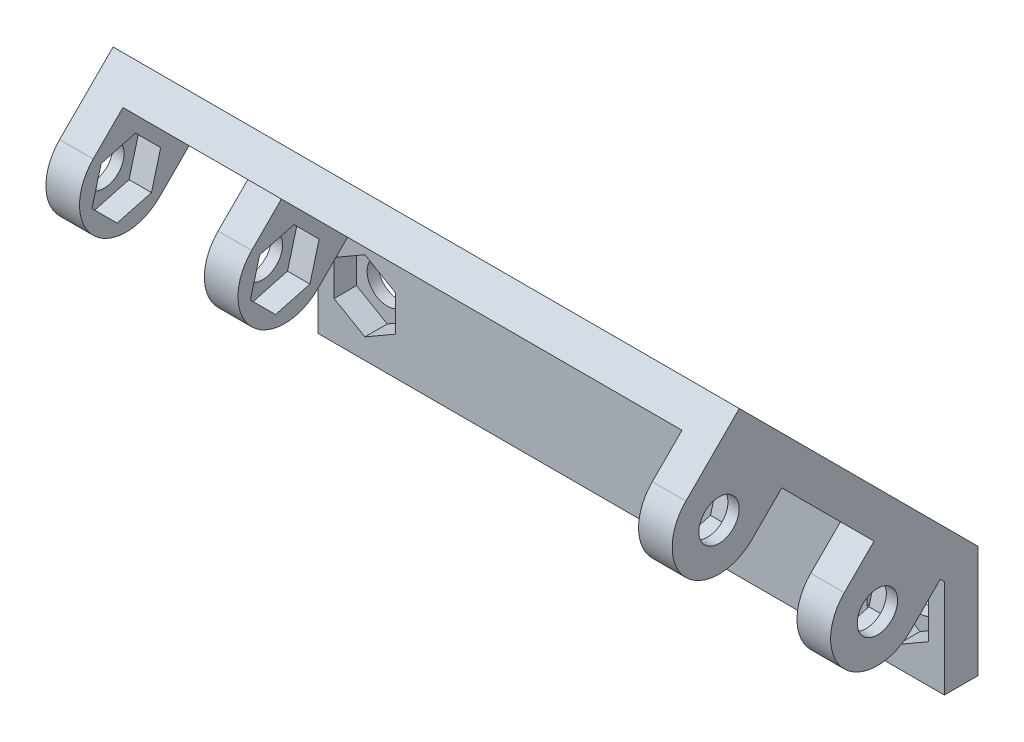
SolidWorks part; units mm, degrees
ref_plane "Front Plane" through (0, 0, 0) normal (0, 0, 1) x (1, 0, 0)
ref_plane "Top Plane" through (0, 0, 0) normal (0, 1, 0) x (1, 0, 0)
ref_plane "Right Plane" through (0, 0, 0) normal (1, 0, 0) x (0, 0, -1)
sketch "Sketch1" plane through (0, 0, 0) normal (0, 0, 1) x (1, 0, 0)
  line L1 (70.0719, -10) -> (14.1792, -10)
  line L2 (70.0719, -10) -> (70.0719, 0)
  line L3 (70.0719, 0) -> (14.1792, 0)
  line L4 (14.1792, -10) -> (14.1792, 0)
extrude "Boss-Extrude1" add sketch "Sketch1" along normal blind 3
sketch "Sketch2" plane through (0, 0, 3) normal (0, 0, 1) x (1, 0, 0)
  line L2 (22.5208, -10) -> (22.5208, 0) construction
  line L3 (14.1792, 0) -> (14.1792, -10) construction
  line L6 (22.5208, -10) -> (22.5208, 0) construction
  line L7 (14.1792, 0) -> (14.1792, -10) construction
  line L8 (42.1255, 0) -> (42.1255, -10) construction
  line L15 (70.0719, 0) -> (14.1792, 0) construction
  line L25 (14.1792, -10) -> (70.0719, -10) construction
  line L26 (14.1792, -5) -> (22.5208, -5) construction
  line L27 (65.9011, -8.1754) -> (63.1511, -6.5877)
  line L28 (21.1, -6.5877) -> (21.1, -3.4123)
  line L29 (21.1, -3.4123) -> (18.35, -1.8246)
  line L30 (18.35, -1.8246) -> (15.6, -3.4123)
  line L31 (15.6, -3.4123) -> (15.6, -6.5877)
  line L32 (15.6, -6.5877) -> (18.35, -8.1754)
  line L33 (18.35, -8.1754) -> (21.1, -6.5877)
  line L34 (68.6511, -6.5877) -> (65.9011, -8.1754)
  line L35 (68.6511, -3.4123) -> (68.6511, -6.5877)
  line L36 (65.9011, -1.8246) -> (68.6511, -3.4123)
  line L37 (63.1511, -3.4123) -> (65.9011, -1.8246)
  line L38 (63.1511, -6.5877) -> (63.1511, -3.4123)
  circle A0 centre (18.35, -5) radius 2.75 construction
  circle A1 centre (65.9011, -5) radius 2.75 construction
  point P14 (15.6, -5)
  dimension "D1" = 5.5
extrude "Cut-Extrude1" cut sketch "Sketch2" against normal blind 2
sketch "Sketch3" plane through (0, 0, 3) normal (0, 0, 1) x (1, 0, 0)
  point P8 (18.35, -5)
  point P11 (65.9011, -5)
hole_wizard "M3 Clearance Hole1" positions "Sketch3" profile "Sketch4" hole size "M3" standard "ANSI Metric" end condition through all
sketch "Sketch4" plane through (18.35, -5, 3) normal (1, 0, 0) x (0, -1, 0)
  line L0 (0, 0) -> (0, 3)
  line L1 (0, 3) -> (1.8, 3)
  line L2 (1.8, 3) -> (1.8, 0)
  line L5 (1.8, 0) -> (0, 0)
  line L11 (0, -6.35) -> (0, 107.95) construction
  dimension "Thru Hole Dia." = 3.6
  dimension "Thru Hole Depth" = 3
sketch "Sketch5" plane through (14.1792, 0, 0) normal (-1, 0, 0) x (0, 0, 1)
  line L0 (0, 0) -> (21.299, 21.299)
  line L1 (21.299, 21.299) -> (23.4203, 19.1777)
  line L2 (23.4203, 19.1777) -> (3, -1.2426)
  line L3 (3, 0) -> (3, -10) construction
  line L4 (3, 0) -> (0, 0) construction
  line L5 (3, 0) -> (22.799, 19.799) construction
  line L6 (3, -1.2426) -> (3, 0)
  line L7 (3, 0) -> (0, 0)
  dimension "D1" = 45
  dimension "D2" = 3
  dimension "D3" = 28
extrude "Boss-Extrude2" add sketch "Sketch5" against normal up to surface (55.8926 mm away) up to face at (70.0719, -5, 1.5)
sketch "Sketch6" plane through (14.1792, 0, 0) normal (-1, 0, 0) x (0, 0, 1)
  line L0 (23.4203, 19.1777) -> (17.5154, 13.2727)
  line L1 (3, -1.2426) -> (23.4203, 19.1777) construction
  line L2 (23.4203, 19.1777) -> (26.072, 16.526)
  line L3 (17.5154, 13.2727) -> (20.167, 10.6211)
  line L4 (11.2754, 11.2754) -> (13.3968, 9.1541) construction
  line L5 (20.8741, 11.3282) -> (23.9413, 10.5063)
  line L6 (23.9413, 10.5063) -> (26.1867, 12.7517)
  line L7 (26.1867, 12.7517) -> (25.3649, 15.8189)
  line L8 (25.3649, 15.8189) -> (22.2976, 16.6408)
  line L9 (22.2976, 16.6408) -> (20.0523, 14.3954)
  line L10 (20.0523, 14.3954) -> (20.8741, 11.3282)
  line L12 (21.299, 21.299) -> (0, 0) construction
  line L13 (5.9101, 0.2533) -> (8.1555, 2.4986)
  line L14 (6.732, -2.814) -> (5.9101, 0.2533)
  line L15 (9.7992, -3.6358) -> (6.732, -2.814)
  line L16 (12.0446, -1.3904) -> (9.7992, -3.6358)
  line L17 (11.2227, 1.6768) -> (12.0446, -1.3904)
  line L18 (8.1555, 2.4986) -> (11.2227, 1.6768)
  line L19 (3.3732, -0.8694) -> (6.0249, -3.5211)
  line L20 (3.3732, -0.8694) -> (9.2782, 5.0355)
  line L21 (9.2782, 5.0355) -> (11.9298, 2.3839)
  arc A0 (26.072, 16.526) -> (20.167, 10.6211) centre (23.1195, 13.5735) cw
  circle A2 centre (23.1195, 13.5735) radius 2.75 construction
  circle A3 centre (8.9774, -0.5686) radius 2.75 construction
  arc A4 (6.0249, -3.5211) -> (11.9298, 2.3839) centre (8.9774, -0.5686) ccw
  point P8 (0, 0)
  point P9 (0, 0)
  point P19 (9.8603, 9.8603)
  point P22 (11.548, 7.3053)
  line M10 (3, -1.2426) -> (23.4203, 19.1777)
  dimension "D3" = 3.75
  dimension "D1" = 1
  dimension "D4" = 5.5
  dimension "D5" = 10
extrude "Boss-Extrude3" add sketch "Sketch6" against normal blind 3 contours L19 A4 L21 L13 L18 L17 L16 L15 L14 M10 | L18 L13 L14 L15 L16 L17 | L9 L10 L5 L6 L7 L8 | A0 L2 L3 L10 L9 L8 L7 L6 L5 M10 region at (14.1792, 17.754, 24.6483) region at (14.1792, 3.6119, 10.5062) region at (14.1792, 13.5735, 23.1195) region at (14.1792, -0.5686, 8.9774)
ref_plane "Plane1" through (42.1255, 0, 0) normal (-1, 0, 0) x (0, 0, 1)
mirror "Mirror1" about plane through (42.1255, 0, 0) normal (-1, 0, 0) of "Boss-Extrude3"
sketch "Sketch7" plane through (14.1792, 0, 0) normal (-1, 0, 0) x (0, 0, 1)
  point P0 (8.9774, -0.5686)
  point P3 (23.1195, 13.5735)
hole_wizard "M3 Clearance Hole2" positions "Sketch7" profile "Sketch8" hole size "M3" standard "ANSI Metric" end condition through all
sketch "Sketch8" plane through (14.1792, -0.5686, 8.9774) normal (0, 1, 0) x (0, 0, 1)
  line L0 (0, 0) -> (0, 55.8926)
  line L1 (0, 55.8926) -> (1.8, 55.8926)
  line L2 (1.8, 55.8926) -> (1.8, 0)
  line L5 (1.8, 0) -> (0, 0)
  line L11 (0, -6.35) -> (0, 107.95) construction
  dimension "Thru Hole Dia." = 3.6
  dimension "Thru Hole Depth" = 55.8926
extrude "Cut-Extrude2" cut sketch "Sketch6<3>" along normal blind 2 from surface contours L18 L13 L14 L15 L16 L17 | L9 L10 L5 L6 L7 L8 region at (14.1792, 13.5735, 23.1195) region at (14.1792, -0.5686, 8.9774) starting at face at (17.1792, -2.3686, 8.9774)
sketch "Sketch6<3>" plane through (14.1792, 0, 0) normal (-1, 0, 0) x (0, 0, 1) same geometry as "Sketch6"
extrude "Cut-Extrude3" cut sketch "Sketch6<4>" against normal blind 2 from surface contours L9 L10 L5 L6 L7 L8 | L18 L13 L14 L15 L16 L17 region at (14.1792, 13.5735, 23.1195) region at (14.1792, -0.5686, 8.9774) starting at face at (67.0719, 15.3735, 23.1195)
sketch "Sketch6<4>" plane through (14.1792, 0, 0) normal (-1, 0, 0) x (0, 0, 1) same geometry as "Sketch6"
